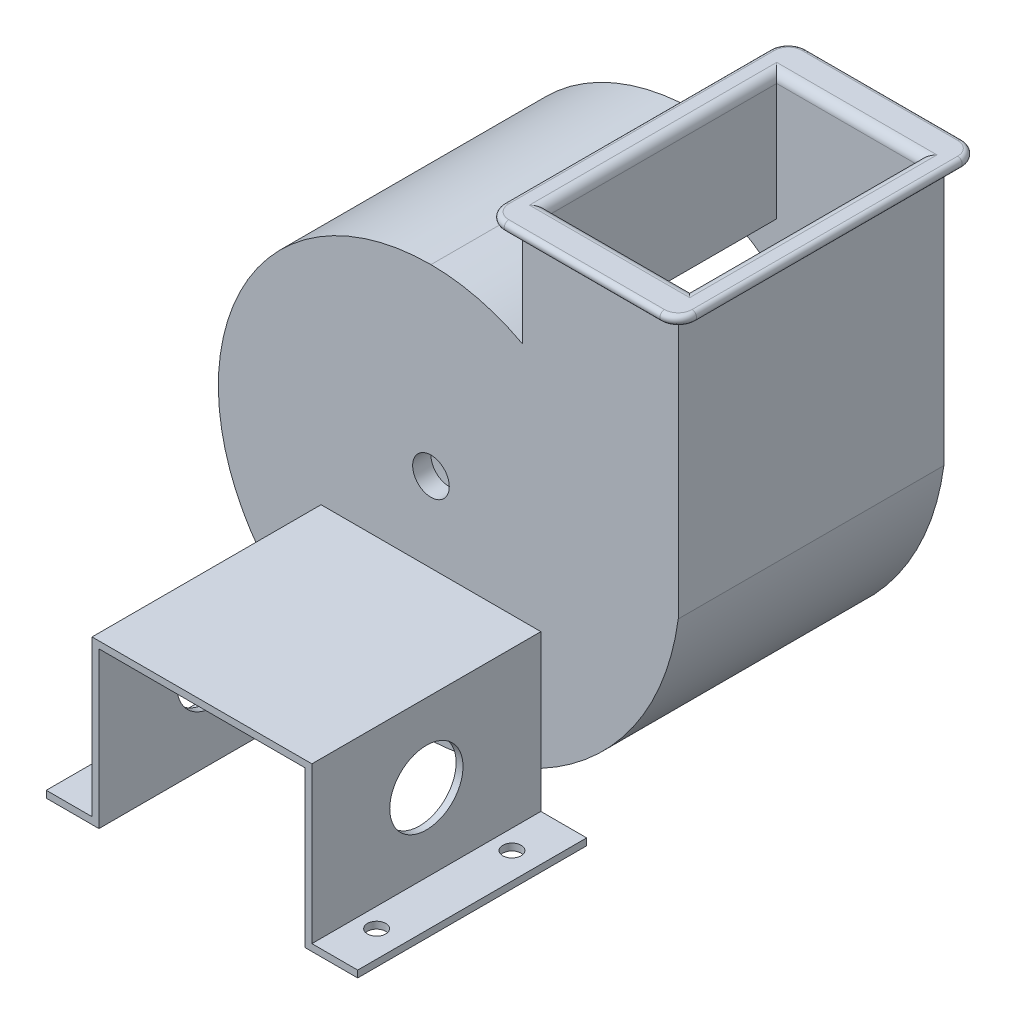
SolidWorks part; units mm, degrees
ref_plane "Front Plane" through (0, 0, 0) normal (0, 0, 1) x (1, 0, 0)
ref_plane "Top Plane" through (0, 0, 0) normal (0, 1, 0) x (1, 0, 0)
ref_plane "Right Plane" through (0, 0, 0) normal (1, 0, 0) x (0, 0, -1)
sketch "Sketch3" plane through (0, 0, 0) normal (0, 0, 1) x (1, 0, 0)
  line L0 (0, 0) -> (-23, 0) construction
  line L1 (0, 0) -> (0, -25) construction
  line L2 (0, 0) -> (27, 0) construction
  line L3 (0, 0) -> (0, 20) construction
  line L4 (27, 0) -> (27, 29)
  line L5 (27, 29) -> (10, 29)
  line L7 (10, 17.5) -> (10, 29)
  circle A0 centre (0, 0) radius 15
  arc A1 (0, 20) -> (-23, 0) centre (0, -3.225) ccw
  arc A2 (-23, 0) -> (0, -25) centre (-1.2309, -3.0524) ccw
  arc A3 (0, -25) -> (27, 0) centre (-1.6166, 3.826) ccw
  arc A4 (0, 20) -> (10, 17.5) centre (0, -1.25) cw
  point P15 (0, 0)
  dimension "D1" = 30
  dimension "D2" = 20
  dimension "D3" = 23
  dimension "D4" = 25
  dimension "D5" = 27
  dimension "D6" = 29
  dimension "D7" = 17
  dimension "D8" = 11.5
extrude "Boss-Extrude1" add sketch "Sketch3" along normal blind 2
sketch "Sketch4" plane through (0, 0, 2) normal (0, 0, 1) x (1, 0, 0)
  line L0 (10.75, 29) -> (10.75, 16.2053)
  line L1 (26.25, 0.0502) -> (26.25, 29)
  line L2 (10, 29) -> (10.75, 29)
  line L3 (27, 0) -> (27, 29)
  line L4 (27, 29) -> (10, 29)
  line L5 (10, 29) -> (10, 17.5)
  line L6 (27, 0) -> (27, 29)
  line L8 (10, 29) -> (10, 17.5)
  line L9 (26.25, 29) -> (27, 29)
  arc A0 (10.75, 16.2053) -> (0, 19.25) centre (0, -1.25) ccw
  arc A1 (0, 19.25) -> (-22.2573, -0.1041) centre (0, -3.225) ccw
  arc A2 (-22.2573, -0.1041) -> (-0.042, -24.2512) centre (-1.2309, -3.0524) ccw
  arc A3 (-0.042, -24.2512) -> (26.25, 0.0502) centre (-1.6166, 3.826) ccw
  arc A4 (-23, 0) -> (0, -25) centre (-1.2309, -3.0524) ccw
  arc A5 (0, -25) -> (27, 0) centre (-1.6166, 3.826) ccw
  arc A6 (10, 17.5) -> (0, 20) centre (0, -1.25) ccw
  arc A7 (0, 20) -> (-23, 0) centre (0, -3.225) ccw
  arc A8 (-23, 0) -> (0, -25) centre (-1.2309, -3.0524) ccw
  arc A9 (0, -25) -> (27, 0) centre (-1.6166, 3.826) ccw
  arc A10 (10, 17.5) -> (0, 20) centre (0, -1.25) ccw
  arc A11 (0, 20) -> (-23, 0) centre (0, -3.225) ccw
  dimension "D1" = 0
  dimension "D2" = 0.75
extrude "Boss-Extrude2" add sketch "Sketch4" along normal blind 25
sketch "Sketch6" plane through (0, 0, 27) normal (0, 0, 1) x (1, 0, 0)
  line L1 (27, 0) -> (27, 29) construction
  line L2 (10, 29) -> (10, 17.5) construction
  line L3 (10, 29) -> (27, 29)
  line L4 (27, 0) -> (27, 29)
  line L5 (10, 29) -> (10, 17.5)
  arc A1 (0, -25) -> (27, 0) centre (-1.6166, 3.826) ccw construction
  arc A2 (-23, 0) -> (0, -25) centre (-1.2309, -3.0524) ccw construction
  arc A3 (10, 17.5) -> (0, 20) centre (0, -1.25) ccw construction
  arc A4 (0, 20) -> (-23, 0) centre (0, -3.225) ccw construction
  arc A6 (0, -25) -> (27, 0) centre (-1.6166, 3.826) ccw
  arc A7 (-23, 0) -> (0, -25) centre (-1.2309, -3.0524) ccw
  arc A8 (10, 17.5) -> (0, 20) centre (0, -1.25) ccw
  arc A9 (0, 20) -> (-23, 0) centre (0, -3.225) ccw
extrude "Boss-Extrude4" add sketch "Sketch6" along normal blind 2
sketch "Sketch7" plane through (0, 0, 29) normal (0, 0, 1) x (1, 0, 0)
  circle A0 centre (0, 0) radius 2
  dimension "D1" = 4
extrude "Cut-Extrude1" cut sketch "Sketch7" against normal blind 2
sketch "Sketch8" plane through (0, 0, 29) normal (0, 0, 1) x (1, 0, 0)
  line L0 (-12, -8.703) -> (12, -8.703)
  line L1 (12, -8.703) -> (12, -25.703)
  line L2 (-12, -8.703) -> (-12, -25.703)
  line L3 (0, 0) -> (0, -21.2471) construction
  line L4 (-12, -25.703) -> (-17, -25.703)
  line L5 (12, -25.703) -> (17, -25.703)
  line L6 (-11.25, -26.453) -> (-17, -26.453)
  line L7 (-11.25, -9.453) -> (-11.25, -26.453)
  line L8 (-11.25, -9.453) -> (11.25, -9.453)
  line L9 (11.25, -9.453) -> (11.25, -26.453)
  line L10 (11.25, -26.453) -> (17, -26.453)
  line L11 (-17, -25.703) -> (-17, -26.453)
  line L12 (17, -25.703) -> (17, -26.453)
  dimension "D1" = 24
  dimension "D2" = 17
  dimension "D3" = 17
  dimension "D4" = 5
  dimension "D5" = 0.75
extrude "Boss-Extrude5" add sketch "Sketch8" along normal blind 25
sketch "Sketch9" plane through (-12, 0, 0) normal (-1, 0, 0) x (0, 0, 1)
  line L0 (29, -8.703) -> (54, -25.703) construction
  circle A0 centre (41.5, -17.203) radius 4
  dimension "D1" = 8
extrude "Cut-Extrude2" cut sketch "Sketch9" against normal through all
sketch "Sketch10" plane through (0, -25.703, 0) normal (0, 1, 0) x (1, 0, 0)
  circle A0 centre (-14.5118, -34.274) radius 1
  circle A1 centre (-14.5118, -49.0543) radius 1
  circle A2 centre (14.1201, -49.0543) radius 1
  circle A3 centre (14.1201, -34.274) radius 1
  dimension "D1" = 2
extrude "Cut-Extrude3" cut sketch "Sketch10" against normal blind 25
sketch "Sketch11" plane through (0, 29, 0) normal (0, 1, 0) x (1, 0, 0)
  line L8 (26.25, -27) -> (26.25, -2) construction
  line L9 (26.25, -27) -> (10.75, -27) construction
  line L10 (10.75, -27) -> (10.75, -2) construction
  line L11 (26.25, -2) -> (10.75, -2) construction
  line L12 (26.25, -27) -> (26.25, -2)
  line L13 (26.25, -27) -> (10.75, -27)
  line L14 (10.75, -27) -> (10.75, -2)
  line L15 (26.25, -2) -> (10.75, -2)
  line L16 (29, 2) -> (8, 2)
  line L17 (8, -31) -> (8, 2)
  line L18 (29, -31) -> (8, -31)
  line L19 (29, -31) -> (29, 2)
sketch "Sketch18" plane through (0, 0, 0) normal (0, 0, -1) x (-1, 0, 0)
  circle A0 centre (0, 0) radius 17.5 construction
  circle A1 centre (1.2481, 17.4554) radius 0.5
  dimension "D1" = 1
  dimension "D2" = 35
extrude "Cut-Extrude4" cut sketch "Sketch18" against normal blind 25
pattern_circular "CirPattern1" count 12 over 360 about axis through (0, 0, 0) along (0, 0, 1) of "Cut-Extrude4"
extrude "Boss-Extrude7" add sketch "Sketch11" along normal blind 1 separate body
fillet "Fillet1" radius 2 4 edges at (29, 29.5, 31) (29, 29.5, -2) (8, 29.5, -2) (8, 29.5, 31)
fillet "Fillet2" 16 edges at (18.5, 30, 31) (28.4142, 30, 30.4142) (29, 30, 14.5) (28.4142, 30, -1.4142) (18.5, 30, -2) (8.5858, 30, -1.4142) (8, 30, 14.5) (8.5858, 30, 30.4142) (29, 29, 14.5) (28.4142, 29, 30.4142) (18.5, 29, 31) (8.5858, 29, 30.4142) (8, 29, 14.5) (8.5858, 29, -1.4142) (18.5, 29, -2) (28.4142, 29, -1.4142) type full round first side face at (18.5, 30, 14.5) second side face at (18.5, 29, 14.5) middle face at (18.5, 29.5, 31) middle face at (8.7929, 29.5, 30.2071) middle face at (8, 29.5, 14.5) middle face at (8.7929, 29.5, -1.2071) middle face at (18.5, 29.5, -2) middle face at (28.2071, 29.5, -1.2071) middle face at (28.2071, 29.5, 30.2071) middle face at (29, 29.5, 14.5)
fillet "Fillet3" radius 1 4 edges at (10.75, 30, 14.5) (18.5, 30, 2) (26.25, 30, 14.5) (18.5, 30, 27)
sketch3d "3DSketch1" plane through (0, 0, 0) normal (0, 0, 1) x (1, 0, 0)
